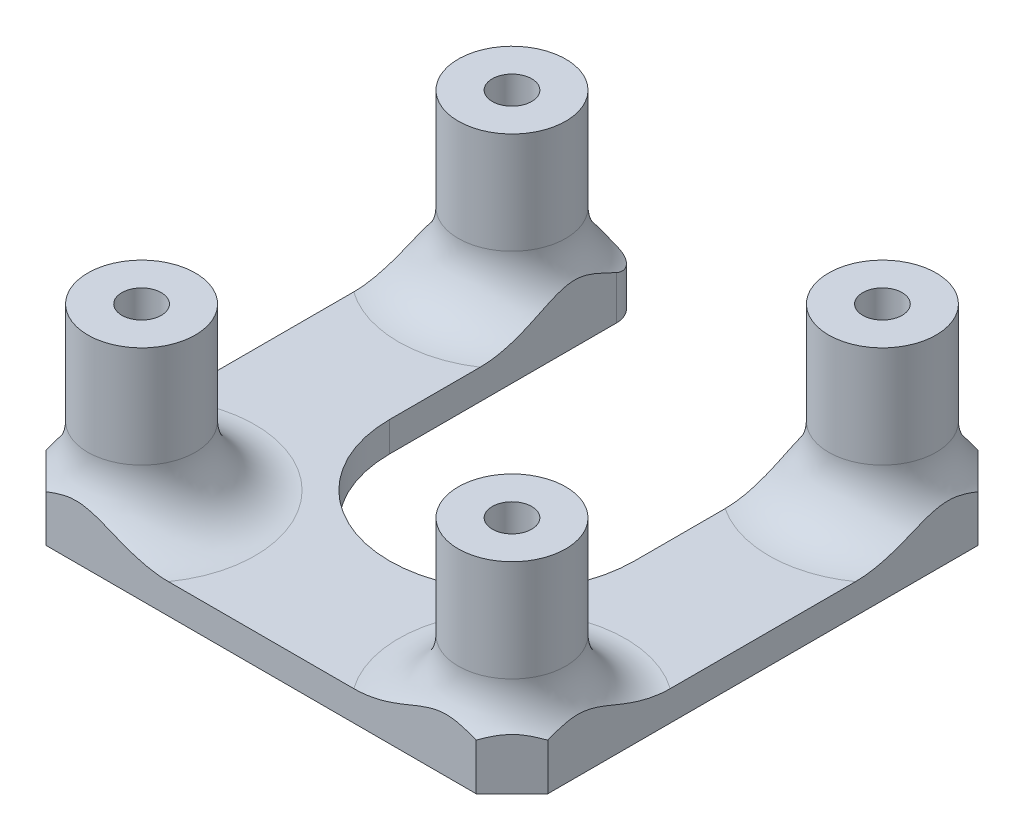
SolidWorks part; units mm, degrees
ref_plane "Alzado" through (0, 0, 0) normal (0, 0, 1) x (1, 0, 0)
ref_plane "Planta" through (0, 0, 0) normal (0, 1, 0) x (1, 0, 0)
ref_plane "Vista lateral" through (0, 0, 0) normal (1, 0, 0) x (0, 0, -1)
sketch "Croquis1" plane through (0, 0, 0) normal (0, 1, 0) x (1, 0, 0)
  line L0 (-10.25, 0) -> (-10.25, 21)
  line L1 (-21, -21) -> (21, -21)
  line L2 (-21, -21) -> (-21, 21)
  line L3 (-21, 21) -> (-10.25, 21)
  line L4 (21, -21) -> (21, 21)
  line L5 (-21, -21) -> (21, 21) construction
  line L6 (-21, 21) -> (21, -21) construction
  line L7 (-15.5, -15.5) -> (15.5, -15.5) construction
  line L8 (-15.5, -15.5) -> (-15.5, 15.5) construction
  line L9 (-15.5, 15.5) -> (15.5, 15.5) construction
  line L10 (15.5, -15.5) -> (15.5, 15.5) construction
  line L11 (-15.5, -15.5) -> (15.5, 15.5) construction
  line L12 (-15.5, 15.5) -> (15.5, -15.5) construction
  line L13 (10.25, 0) -> (10.25, 21)
  line L14 (10.25, 21) -> (21, 21)
  circle A0 centre (-15.5, 15.5) radius 1.65
  circle A1 centre (15.5, 15.5) radius 1.65
  circle A2 centre (15.5, -15.5) radius 1.65
  circle A3 centre (-15.5, -15.5) radius 1.65
  arc A4 (-10.25, 0) -> (10.25, 0) centre (0, 0) ccw
  point P0 (0, 0)
  point P6 (0, 0)
  dimension "D5" = 3.3
  dimension "D6" = 20.5
  dimension "D1" = 42
  dimension "D2" = 42
  dimension "D3" = 31
  dimension "D4" = 31
extrude "Saliente-Extruir1" add sketch "Croquis1" along normal blind 2.5
chamfer "Chaflán1" distance 3 angle 45 4 edges at (-21, 1.25, 21) (21, 1.25, 21) (-21, 1.25, -21) (21, 1.25, -21)
fillet "Redondeo1" radius 2 2 edges at (10.25, 1.25, -21) (-10.25, 1.25, -21)
sketch "Croquis2" plane through (0, 2.5, 0) normal (0, 1, 0) x (1, 0, 0)
  circle A0 centre (-15.5, 15.5) radius 4.5
  circle A1 centre (15.5, 15.5) radius 4.5
  circle A2 centre (15.5, -15.5) radius 4.5
  circle A3 centre (-15.5, -15.5) radius 4.5
  circle A4 centre (-15.5, -15.5) radius 1.65 construction
  circle A5 centre (15.5, -15.5) radius 1.65 construction
  circle A6 centre (15.5, 15.5) radius 1.65 construction
  circle A7 centre (-15.5, 15.5) radius 1.65 construction
  circle A8 centre (-15.5, -15.5) radius 1.65
  circle A9 centre (15.5, -15.5) radius 1.65
  circle A10 centre (15.5, 15.5) radius 1.65
  circle A11 centre (-15.5, 15.5) radius 1.65
  dimension "D1" = 9
extrude "Saliente-Extruir2" add sketch "Croquis2" along normal blind 13.5
fillet "Redondeo2" radius 5 4 edges at (-15.5, 2.5, 20) (15.5, 2.5, 20) (15.5, 2.5, -11) (-15.5, 2.5, -11)
fillet "Redondeo3" radius 1 4 edges at (-15.5, 0, -13.85) (-15.5, 0, 17.15) (15.5, 0, 17.15) (15.5, 0, -13.85)
